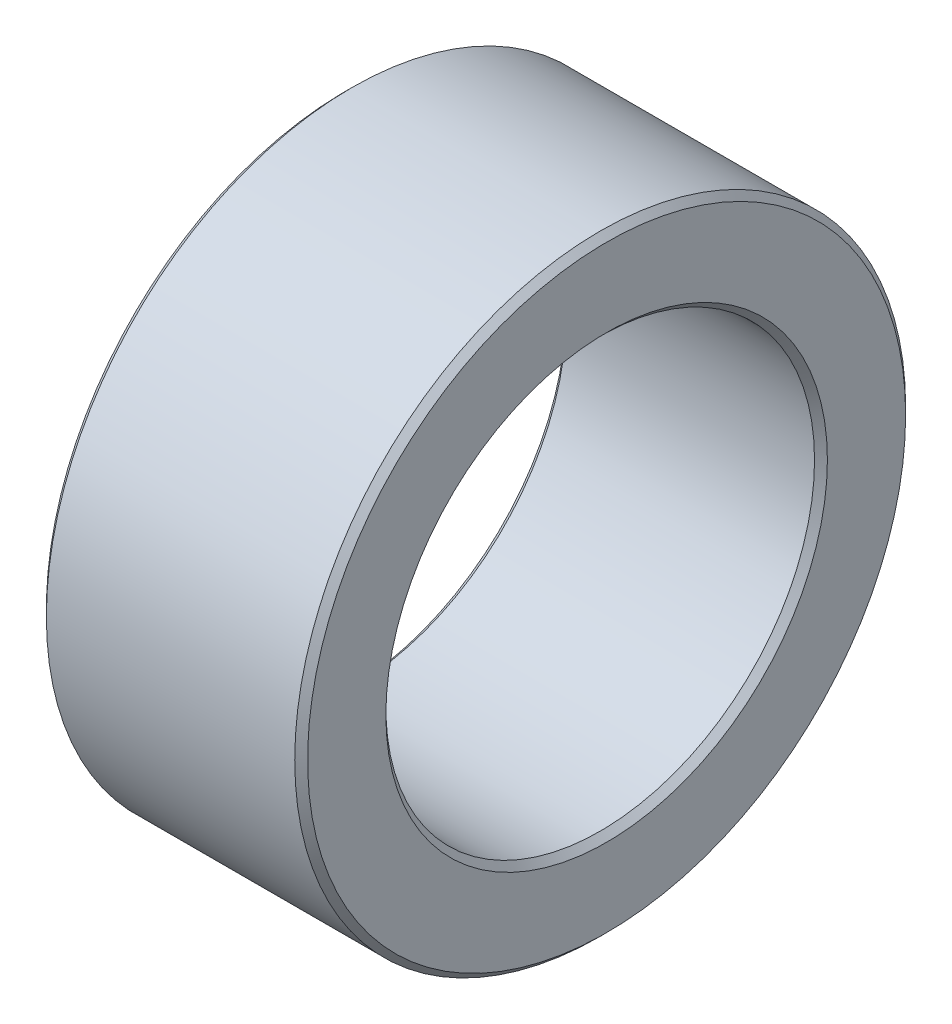
SolidWorks part; units mm, degrees
material "6061-T6 (SS)"
ref_plane "Front Plane" through (0, 0, 0) normal (0, 0, 1) x (1, 0, 0)
ref_plane "Top Plane" through (0, 0, 0) normal (0, 1, 0) x (1, 0, 0)
ref_plane "Right Plane" through (0, 0, 0) normal (1, 0, 0) x (0, 0, -1)
sketch "Sketch1" plane through (0, 0, 0) normal (1, 0, 0) x (0, 0, -1)
  circle A0 centre (0, 0) radius 25.4
  circle A1 centre (0, 0) radius 36.195
  dimension "D1" = 72.39
  dimension "D2" = 50.8
extrude "Boss-Extrude1" add sketch "Sketch1" along normal blind 30.9562
chamfer "Chamfer1" distance 0.762 angle 45 4 edges at (0, 0, -25.4) (30.9562, 0, -25.4) (30.9562, 0, -36.195) (0, 0, -36.195)
